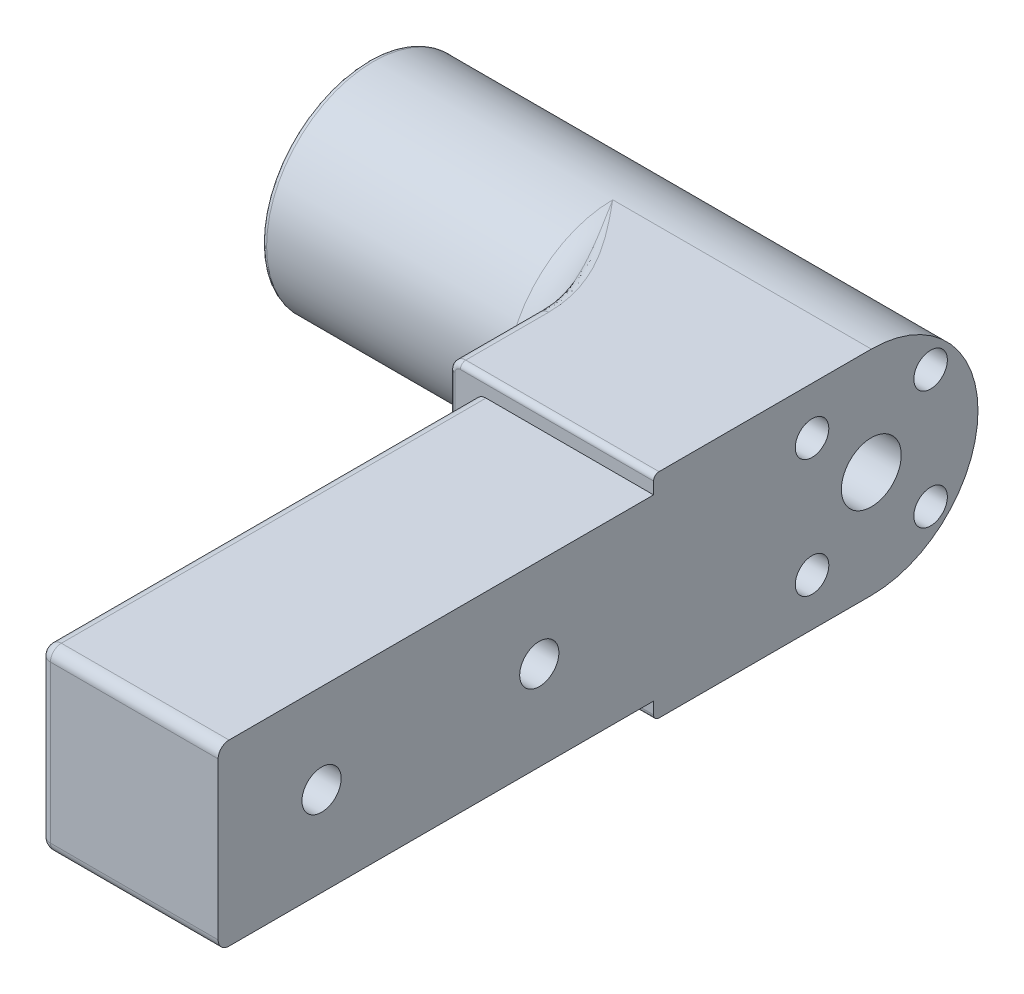
SolidWorks part; units mm, degrees
ref_plane "Front Plane" through (0, 0, 0) normal (0, 0, 1) x (1, 0, 0)
ref_plane "Top Plane" through (0, 0, 0) normal (0, 1, 0) x (1, 0, 0)
ref_plane "Right Plane" through (0, 0, 0) normal (1, 0, 0) x (0, 0, -1)
sketch "Sketch1" plane through (0, 0, 0) normal (1, 0, 0) x (0, 0, -1)
  line L0 (0, 0) -> (-25.4, 0) construction
  line L1 (0, 0) -> (6.9148, 6.9148) construction
  line L8 (-25.4, -12.446) -> (0, -12.446)
  line L9 (-25.4, -12.446) -> (-25.4, 12.446)
  line L10 (-25.4, 12.446) -> (0, 12.446)
  line L11 (0, -12.446) -> (0, 12.446)
  line L12 (-25.4, -12.446) -> (0, 12.446) construction
  line L13 (-25.4, 12.446) -> (0, -12.446) construction
  circle A0 centre (0, 0) radius 12.446
  circle A1 centre (6.9148, 6.9148) radius 1.9558
  circle A5 centre (9.779, 0) radius 1.9558 construction
  circle A6 centre (6.9148, -6.9148) radius 1.9558
  circle A7 centre (0, -9.779) radius 1.9558 construction
  circle A8 centre (-6.9148, -6.9148) radius 1.9558
  circle A9 centre (-9.779, 0) radius 1.9558 construction
  circle A10 centre (-6.9148, 6.9148) radius 1.9558
  circle A11 centre (0, 9.779) radius 1.9558 construction
  circle A12 centre (0, 0) radius 3.4925
  point P4 (-12.7, 0)
  point P5 (-28.4742, 0)
  point P7 (-25.4, 0)
  point P34 (0, 0)
  dimension "D1" = 24.892
  dimension "D5" = 3.9116
  dimension "D9" = 6.985
  dimension "D3" = 25.4
  dimension "D6" = 9.779
  dimension "D8" = 45
  dimension "D7" = 8
extrude "Boss-Extrude1" add sketch "Sketch1" along normal blind 11.1125 and the other way blind 12.7 contours A12 L11 A7 A0 A11 A6 A5 A1 | A12 L11 A11 A0 A10 A8 A7 | A0 L9 | A0 L10 L9 | A10 A0 A8 A9 | A0 L9 L8 region at (0, 0, 17.3406) region at (0, 0, 5.45) region at (0, 0, -5.45)
sketch "Sketch2" plane through (0, 0, 25.4) normal (0, 0, 1) x (1, 0, 0)
  line L0 (11.1125, -12.446) -> (11.1125, 12.446) construction
  line L5 (11.1125, -10.414) -> (-9.7155, -10.414)
  line L6 (11.1125, -10.414) -> (11.1125, 10.414)
  line L7 (11.1125, 10.414) -> (-9.7155, 10.414)
  line L8 (-9.7155, -10.414) -> (-9.7155, 10.414)
  line L9 (-12.7, -12.446) -> (-12.7, 12.446) construction
  point P0 (0, 0)
  point P8 (-9.7155, 0)
  point P9 (-12.7, 0)
  dimension "D1" = 20.828
  dimension "D2" = 20.828
extrude "Boss-Extrude2" add sketch "Sketch2" along normal blind 50.8
sketch "Sketch3" plane through (-12.7, 0, 0) normal (-1, 0, 0) x (0, 0, 1)
  circle A0 centre (0, 0) radius 12.446
  arc A1 (0, 12.446) -> (0, -12.446) centre (0, 0) ccw construction
  circle A2 centre (0, 0) radius 3.4925 construction
  circle A3 centre (-6.9148, -6.9148) radius 1.9558 construction
  circle A5 centre (-6.9148, 6.9148) radius 1.9558 construction
  circle A7 centre (6.9148, 6.9148) radius 1.9558 construction
  circle A9 centre (6.9148, -6.9148) radius 1.9558 construction
  circle A11 centre (0, 0) radius 3.4925
  circle A12 centre (-6.9148, -6.9148) radius 1.9558
  circle A14 centre (-6.9148, 6.9148) radius 1.9558
  circle A16 centre (6.9148, 6.9148) radius 1.9558
  circle A18 centre (6.9148, -6.9148) radius 1.9558
extrude "Boss-Extrude3" add sketch "Sketch3" along normal blind 34.925
sketch "Sketch6" plane through (-9.7155, 0, 0) normal (-1, 0, 0) x (0, 0, 1)
  line L0 (76.2, 0) -> (25.4, 0) construction
  line L1 (76.2, 10.414) -> (76.2, -10.414) construction
  line L2 (25.4, 10.414) -> (25.4, -10.414) construction
  circle A0 centre (38.735, 0) radius 2.286
  circle A1 centre (64.135, 0) radius 2.286
  circle A2 centre (38.735, 0) radius 2.1828 construction
  circle A3 centre (38.735, 0) radius 2.1828 construction
  circle A4 centre (64.135, 0) radius 2.1828 construction
  circle A5 centre (64.135, 0) radius 2.1828 construction
  dimension "D2" = 4.572
extrude "Cut-Extrude2" cut sketch "Sketch6" against normal up to surface (20.828 mm away) up to face at (11.1125, 0, -3.4925)
fillet "Fillet1" radius 6.35 1 edges at (-12.7, 0, 12.446)
fillet "Fillet2" radius 1.27 9 edges at (-12.7, -12.446, 19.7425) (-12.7, 12.446, 19.7425) (-9.7155, -10.414, 50.8) (-13.4496, -12.446, 9.738) (-13.4496, 12.446, 9.738) (-9.7155, 0, 76.2) (0.6985, -10.414, 76.2) (0.6985, 10.414, 76.2) (-9.7155, 10.414, 50.8)
fillet "Fillet3" radius 0.635 6 edges at (-0.1588, -12.446, 25.4) (-12.328, -12.074, 25.4) (-0.1588, 12.446, 25.4) (-12.328, 12.074, 25.4) (-12.7, 0, 25.4) (-47.625, 0, 12.446)
